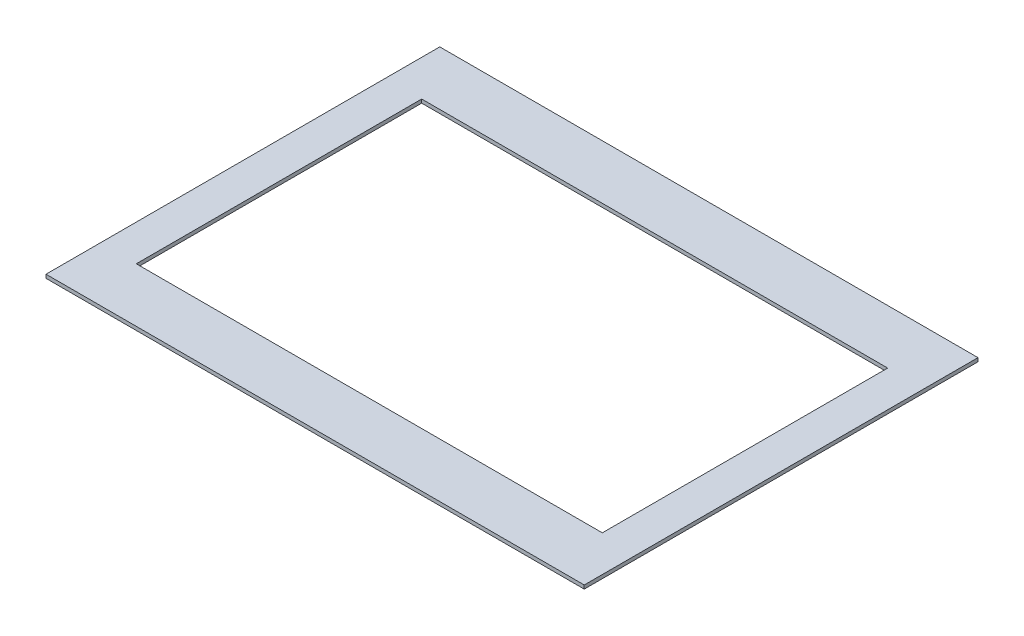
SolidWorks part; units mm, degrees
ref_plane "Front Plane" through (0, 0, 0) normal (0, 0, 1) x (1, 0, 0)
ref_plane "Top Plane" through (0, 0, 0) normal (0, 1, 0) x (1, 0, 0)
ref_plane "Right Plane" through (0, 0, 0) normal (1, 0, 0) x (0, 0, -1)
sketch "Sketch1" plane through (0, 0, 0) normal (1, 0, 0) x (0, 0, -1)
  line L0 (-26.6783, 0) -> (191.3217, 0)
  line L1 (119.9, 0) -> (-119.9, 0) construction
  line L2 (-26.6783, 0) -> (-26.6783, 2)
  line L3 (191.3217, 0) -> (191.3217, 2)
  line L4 (191.3217, 2) -> (-26.6783, 2)
  dimension "D1" = 218
  dimension "D2" = 2
extrude "Boss-Extrude1" add sketch "Sketch1" along normal blind 298 contours L4 L2 L0 L3
sketch "Sketch2" plane through (0, 2, 0) normal (0, 1, 0) x (1, 0, 0)
  line L0 (0, -1.1) -> (0, 1.1) construction
  line L1 (20, 161.3217) -> (278, 161.3217)
  line L2 (20, 161.3217) -> (20, 3.3217)
  line L3 (20, 3.3217) -> (278, 3.3217)
  line L4 (278, 161.3217) -> (278, 3.3217)
  line L5 (298, 191.3217) -> (298, -26.6783) construction
  line L6 (298, -26.6783) -> (0, -26.6783) construction
  line L7 (298, 191.3217) -> (0, 191.3217) construction
  dimension "D1" = 20
  dimension "D2" = 20
  dimension "D3" = 30
  dimension "D4" = 30
extrude "Cut-Extrude1" cut sketch "Sketch2" against normal blind 10
